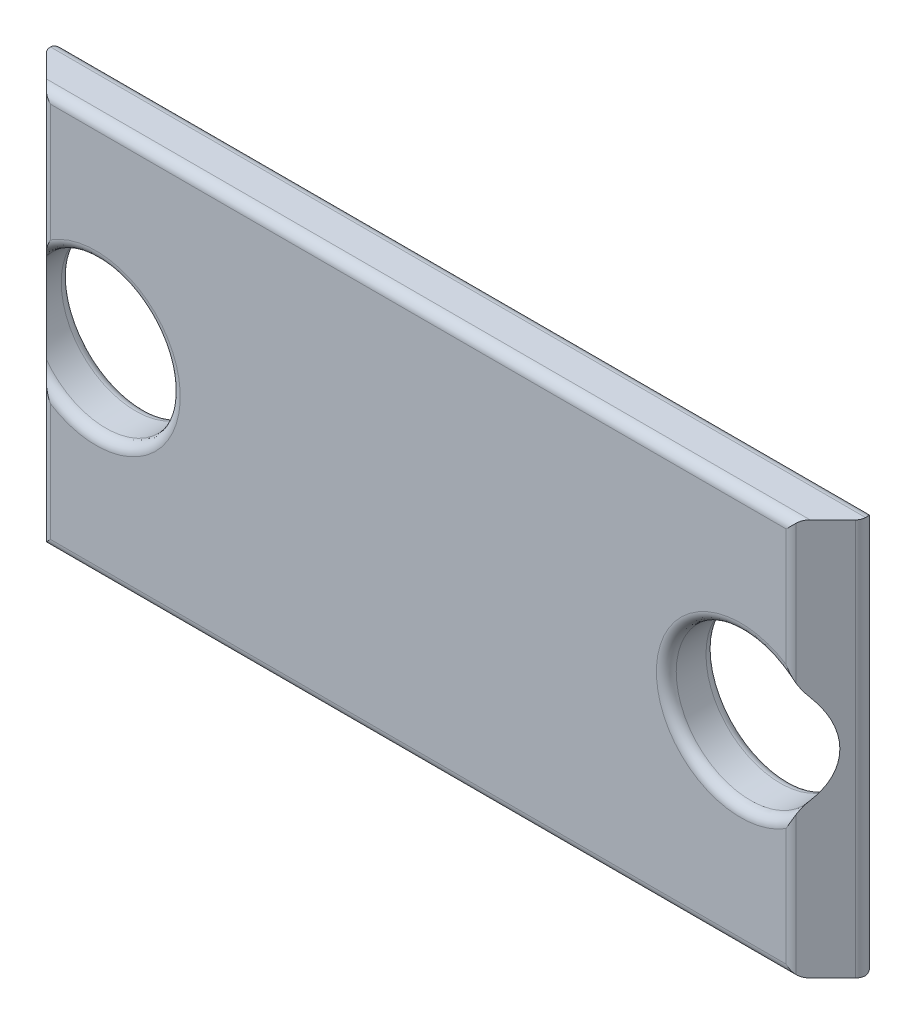
SolidWorks part; units mm, degrees
ref_plane "Front" through (0, 0, 0) normal (0, 0, 1) x (1, 0, 0)
ref_plane "Top" through (0, 0, 0) normal (0, 1, 0) x (1, 0, 0)
ref_plane "Right" through (0, 0, 0) normal (1, 0, 0) x (0, 0, -1)
sketch "Esquisse1" plane through (0, 0, 0) normal (0, 0, 1) x (1, 0, 0)
  line L0 (8.5, 4) -> (8.5, 8) construction
  line L1 (0, 0) -> (17, 0)
  line L2 (0, 0) -> (0, 8)
  line L3 (0, 8) -> (17, 8)
  line L4 (17, 0) -> (17, 8)
  line L5 (15, 4) -> (2, 4) construction
  circle A0 centre (2, 4) radius 1.5
  circle A1 centre (15, 4) radius 1.5
  point P8 (8.5, 4)
  dimension "D3" = 13
  dimension "D4" = 3
  dimension "D5" = 3
  dimension "D1" = 8
  dimension "D2" = 17
  dimension "D6" = 4
extrude "Boss.-Extru.1" add sketch "Esquisse1" along normal blind 1
chamfer "Chanfrein1" distance 1 angle 45 2 edges at (17, 4, 1) (0, 4, 1)
fillet "Congé1" radius 0.2 14 edges at (16.5, 4, 0) (8.5, 0, 0) (17, 4, 0) (8.5, 8, 0) (0, 4, 0) (3.5, 4, 0) (1, 1.441, 1) (3.5, 4, 1) (1, 6.559, 1) (8.5, 8, 1) (16, 6.559, 1) (13.5, 4, 1) (16, 1.441, 1) (8.5, 0, 1)
